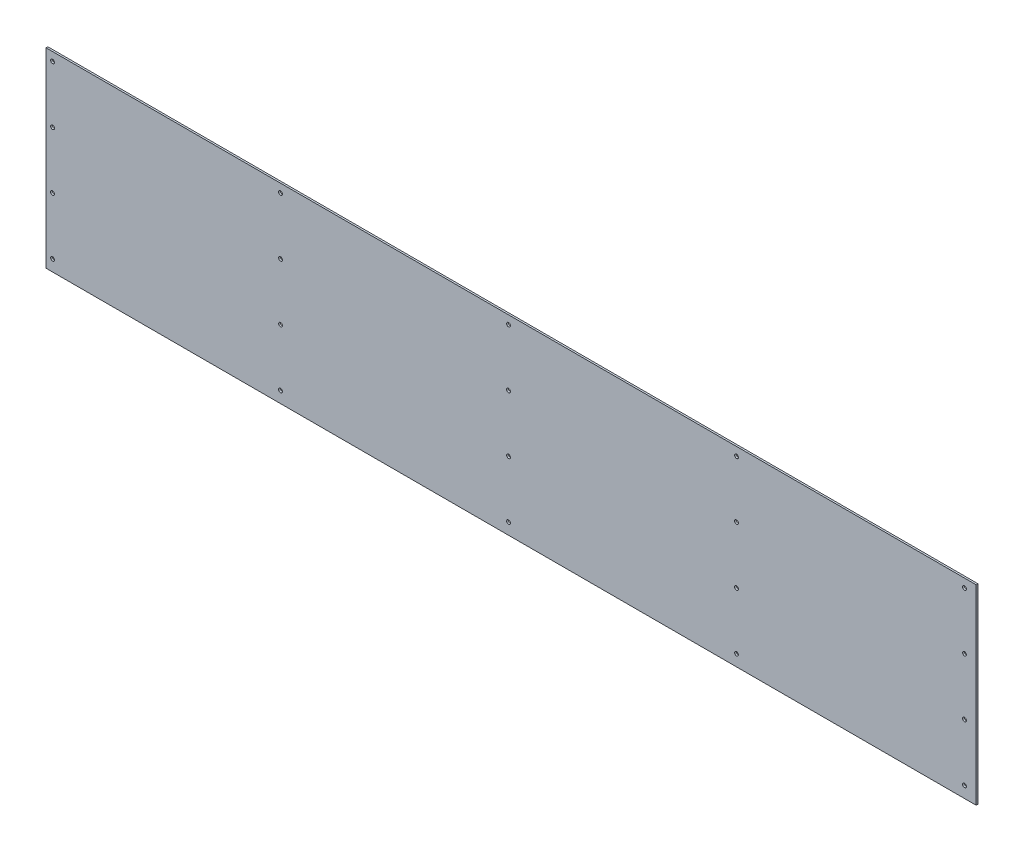
SolidWorks part; units mm, degrees
ref_plane "Alzado" through (0, 0, 0) normal (0, 0, 1) x (1, 0, 0)
ref_plane "Planta" through (0, 0, 0) normal (0, 1, 0) x (1, 0, 0)
ref_plane "Vista lateral" through (0, 0, 0) normal (1, 0, 0) x (0, 0, -1)
sketch "Croquis1" plane through (0, 0, 0) normal (0, 0, 1) x (1, 0, 0)
  line L1 (-326.8059, 168.0659) -> (1305.1941, 168.0659)
  line L2 (-326.8059, 168.0659) -> (-326.8059, -166.9341)
  line L3 (-326.8059, -166.9341) -> (1305.1941, -166.9341)
  line L4 (1305.1941, 168.0659) -> (1305.1941, -166.9341)
  dimension "D1" = 335
  dimension "D2" = 1632
base flange "Brida base1" sketch "Croquis1" thickness 3.175 reverse thickness direction no parameters "D1"=0.7366
hole_wizard "Taladro de margen para 1/41" positions "Croquis7" profile "Croquis6" hole size "1/4" standard "Ansi Inch" end condition up to next
sketch "Croquis7" plane through (0, 0, 0) normal (0, 0, 1) x (1, 0, 0)
  line L0 (1305.1941, -166.9341) -> (1305.1941, 168.0659) construction
  line L1 (1305.1941, 168.0659) -> (-326.8059, 168.0659) construction
  point P0 (1284.6941, 153.0659)
  point P13 (884.6941, 153.0659)
  point P14 (484.6941, 153.0659)
  point P15 (84.6941, 153.0659)
  point P16 (-315.3059, 153.0659)
  point P17 (884.6941, 53.0659)
  point P18 (484.6941, 53.0659)
  point P19 (84.6941, 53.0659)
  point P20 (-315.3059, 53.0659)
  point P21 (884.6941, -46.9341)
  point P22 (484.6941, -46.9341)
  point P23 (84.6941, -46.9341)
  point P24 (-315.3059, -46.9341)
  point P25 (884.6941, -146.9341)
  point P26 (484.6941, -146.9341)
  point P27 (84.6941, -146.9341)
  point P28 (-315.3059, -146.9341)
  point P29 (1284.6941, 53.0659)
  point P30 (1284.6941, -46.9341)
  point P31 (1284.6941, -146.9341)
  dimension "D1" = 20.5
  dimension "D2" = 15
  dimension "D3" = 5
  dimension "D4" = 4
sketch "Croquis6" plane through (1284.6941, 153.0659, 0) normal (1, 0, 0) x (0, -1, 0)
  line L0 (0, 0) -> (0, 3.175)
  line L1 (0, 3.175) -> (3.3782, 3.175)
  line L2 (3.3782, 3.175) -> (3.3782, 0)
  line L5 (3.3782, 0) -> (0, 0)
  line L11 (0, -6.35) -> (0, 107.95) construction
  dimension "Diámetro de taladro hasta el siguiente" = 6.7564
  dimension "Profundidad de taladro hasta el siguiente" = 3.175
sketch "Líneas de pliegue1" [suppressed] plane through (0, 0, 0) normal (0, 1, 0) x (1, 0, 0)
sketch "Cuadro delimitador1" [suppressed] plane through (0, 0, 0) normal (0, 1, 0) x (1, 0, 0)
sheet metal parameters "Chapa metálica1" thickness 3.175 parameters "D1"=0.7366
flat pattern "Chapa desplegada1" [suppressed]
sketch "Líneas de pliegue2" plane through (0, 0, 0) normal (0, 1, 0) x (1, 0, 0)
sketch3d "Cuadro delimitador2" [suppressed]
  line L0 (326.8059, -166.9341, 0) -> (-1305.1941, -166.9341, 0) construction
  line L1 (326.8059, 168.0659, 0) -> (-1305.1941, 168.0659, 0) construction
  line L2 (326.8059, -166.9341, 0) -> (326.8059, 168.0659, 0) construction
  line L3 (-1305.1941, -166.9341, 0) -> (-1305.1941, 168.0659, 0) construction
sheet metal parameters "Chapa metálica2" thickness 3.175 parameters "D1"=0.7366
flat pattern "Chapa desplegada1"
sketch "Líneas de pliegue2" plane through (0, 0, 0) normal (0, 1, 0) x (1, 0, 0)
sketch3d "Cuadro delimitador2" [suppressed]
  line L0 (-326.8059, -166.9341, 0) -> (1305.1941, -166.9341, 0) construction
  line L1 (-326.8059, 168.0659, 0) -> (1305.1941, 168.0659, 0) construction
  line L2 (-326.8059, -166.9341, 0) -> (-326.8059, 168.0659, 0) construction
  line L3 (1305.1941, -166.9341, 0) -> (1305.1941, 168.0659, 0) construction
